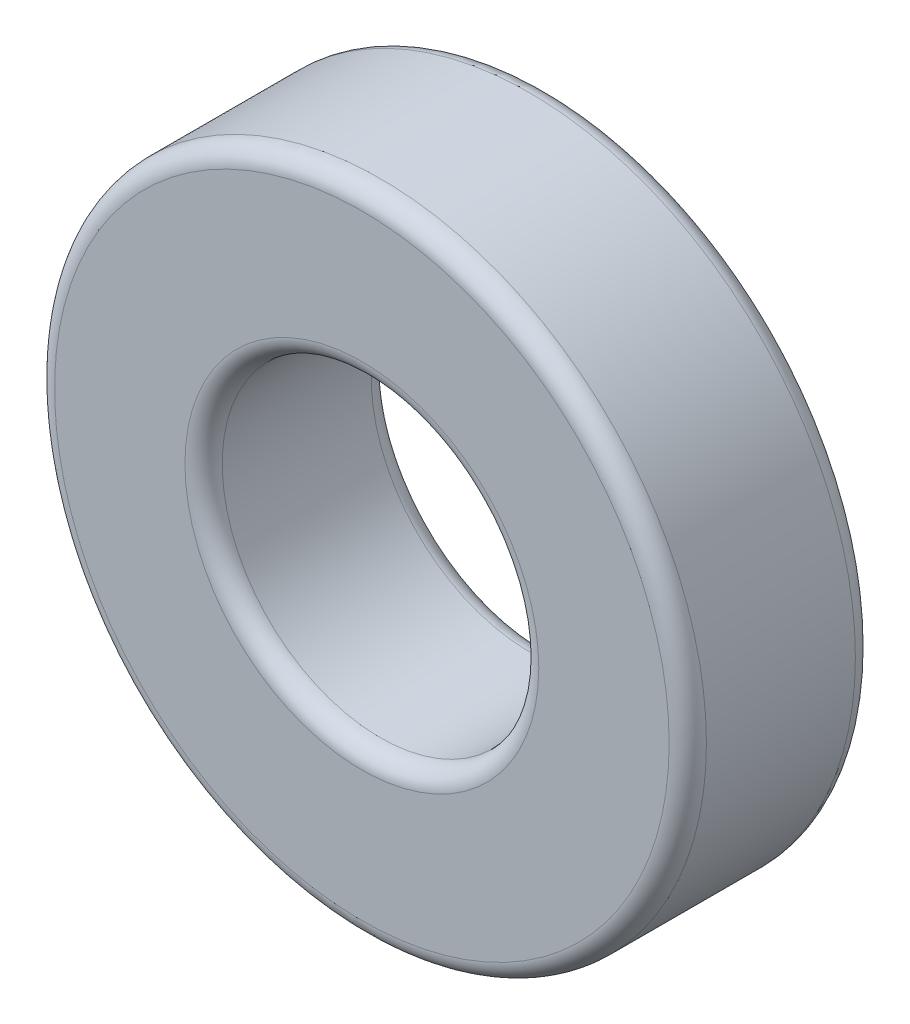
SolidWorks part; units mm, degrees
ref_plane "Front Plane" through (0, 0, 0) normal (0, 0, 1) x (1, 0, 0)
ref_plane "Top Plane" through (0, 0, 0) normal (0, 1, 0) x (1, 0, 0)
ref_plane "Right Plane" through (0, 0, 0) normal (1, 0, 0) x (0, 0, -1)
sketch "Sketch1" plane through (0, 0, 0) normal (0, 0, 1) x (1, 0, 0)
  circle A0 centre (0, 0) radius 8.5
  circle A1 centre (0, 0) radius 17.5
  dimension "D1" = 35
  dimension "D2" = 17
extrude "Boss-Extrude1" add sketch "Sketch1" along normal blind 10
fillet "Fillet1" radius 1 4 edges at (8.5, 0, 0) (8.5, 0, 10) (17.5, 0, 0) (17.5, 0, 10)
